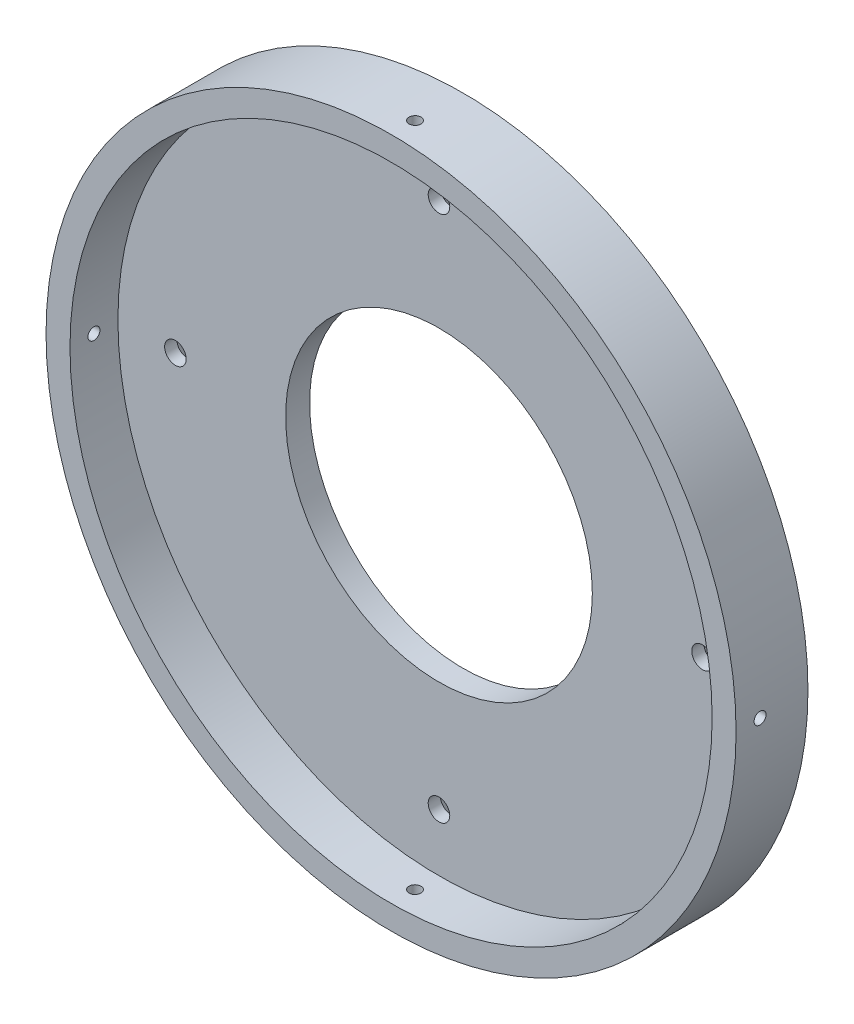
SolidWorks part; units mm, degrees
ref_plane "Front Plane" through (0, 0, 0) normal (0, 0, 1) x (1, 0, 0)
ref_plane "Top Plane" through (0, 0, 0) normal (0, 1, 0) x (1, 0, 0)
ref_plane "Right Plane" through (0, 0, 0) normal (1, 0, 0) x (0, 0, -1)
sketch "Sketch1" plane through (0, 0, 0) normal (0, 0, 1) x (1, 0, 0)
  circle A0 centre (0, 0) radius 72
  circle A1 centre (0, 0) radius 32
  dimension "D1" = 144
  dimension "D2" = 40
extrude "Boss-Extrude1" add sketch "Sketch1" along normal blind 5
sketch "Sketch2" plane through (0, 0, 5) normal (0, 0, 1) x (1, 0, 0)
  circle A0 centre (0, 0) radius 67
  circle A1 centre (0, 0) radius 72
  circle A2 centre (0, 0) radius 72
  dimension "D1" = 0
  dimension "D2" = 5
extrude "Boss-Extrude2" add sketch "Sketch2" along normal blind 10
sketch "Sketch3" plane through (0, 0, 0) normal (0, 1, 0) x (1, 0, 0)
  line L0 (-72, -15) -> (72, -15) construction
  circle A0 centre (0, -10) radius 1.25
  dimension "D2" = 2.5
  dimension "D1" = 5
extrude "Cut-Extrude1" cut sketch "Sketch3" against normal up to surface (72 mm away) up to face at (72, 0, 0)
pattern_circular "CirPattern1" count 4 over 360 about axis through (0, 0, 5) along (0, 0, -1) of "Cut-Extrude1"
sketch "Sketch9" plane through (0, 0, 0) normal (0, 0, -1) x (-1, 0, 0)
  point P0 (0, 55)
  point P4 (55, 0)
  point P6 (0, -55)
  point P8 (-55, 0)
  dimension "D1" = 55
  dimension "D2" = 0
  dimension "D3" = 55
  dimension "D4" = 55
  dimension "D5" = 55
hole_wizard "CSK for M4 Countersunk Flat Head Screw3" positions "Sketch9" profile "Sketch10" countersink size "M4" standard "ISO" end condition through all
sketch "Sketch10" plane through (0, 55, 0) normal (1, 0, 0) x (0, 1, 0)
  line L0 (0, 0) -> (0, 15)
  line L1 (0, 15) -> (2.25, 15)
  line L2 (2.25, 15) -> (2.25, 2.45)
  line L3 (2.25, 2.45) -> (4.7, 0)
  line L5 (4.7, 0) -> (0, 0)
  line L6 (-2.25, 2.45) -> (-4.7, 0) construction
  line L11 (0, -6.35) -> (0, 107.95) construction
  dimension "Thru Hole Dia." = 4.5
  dimension "Thru Hole Depth" = 15
  dimension "Near C'Sink Dia." = 9.4
  dimension "Near C'Sink Angle" = 90
